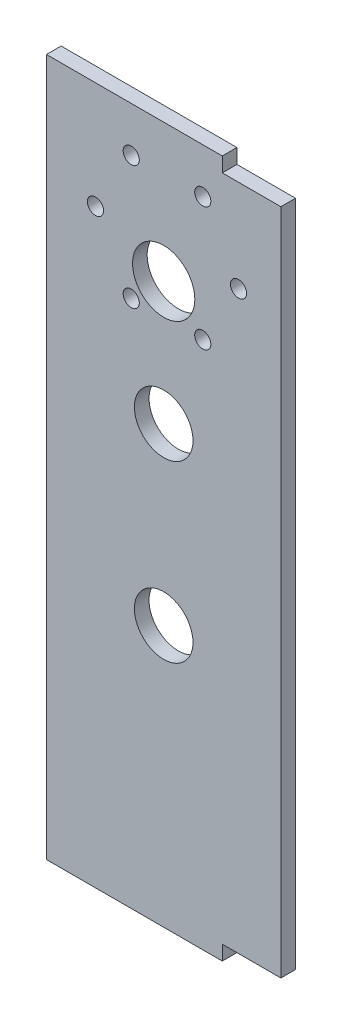
SolidWorks part; units mm, degrees
ref_plane "Спереди" through (0, 0, 0) normal (0, 0, 1) x (1, 0, 0)
ref_plane "Сверху" through (0, 0, 0) normal (0, 1, 0) x (1, 0, 0)
ref_plane "Справа" through (0, 0, 0) normal (1, 0, 0) x (0, 0, -1)
sketch "Эскиз1" plane through (0, 0, 0) normal (0, 0, 1) x (1, 0, 0)
  line L0 (6.35, 75.565) -> (6.35, 151.13) construction
  line L1 (19.05, 151.13) -> (-19.05, 151.13)
  line L13 (19.05, 0) -> (-19.05, 0)
  line L15 (-19.05, 0) -> (-19.05, 151.13)
  line L16 (19.05, 0) -> (19.05, 3.175)
  line L17 (19.05, 3.175) -> (31.75, 3.175)
  line L18 (31.75, 3.175) -> (31.75, 147.955)
  line L19 (31.75, 147.955) -> (19.05, 147.955)
  line L20 (19.05, 147.955) -> (19.05, 151.13)
  line L21 (-19.05, 75.565) -> (31.75, 75.565) construction
  line L22 (6.35, 75.565) -> (6.35, 107.9679) construction
  line L23 (22.5681, 127.955) -> (14.8181, 141.3784) construction
  line L24 (14.8181, 141.3784) -> (-0.6819, 141.3784) construction
  line L25 (-0.6819, 141.3784) -> (-8.4319, 127.955) construction
  line L26 (-8.4319, 127.955) -> (-0.6819, 114.5316) construction
  line L27 (-0.6819, 114.5316) -> (14.8181, 114.5316) construction
  line L28 (14.8181, 114.5316) -> (22.5681, 127.955) construction
  circle A0 centre (6.35, 56.6308) radius 18.9342 construction
  circle A8 centre (6.35, 94.4992) radius 18.9342 construction
  circle A9 centre (6.35, 121.2433) radius 6.75
  circle A10 centre (7.0681, 127.955) radius 13.4234 construction
  circle A12 centre (22.5681, 127.955) radius 1.75
  circle A13 centre (14.8181, 114.5316) radius 1.75
  circle A14 centre (-0.6819, 114.5316) radius 1.75
  circle A15 centre (-8.4319, 127.955) radius 1.75
  circle A16 centre (-0.6819, 141.3784) radius 1.75
  circle A17 centre (14.8181, 141.3784) radius 1.75
  circle A19 centre (7.0681, 127.955) radius 20 construction
  circle A20 centre (6.35, 121.2433) radius 7.81 construction
  circle A21 centre (6.35, 94.4992) radius 6.35
  circle A22 centre (6.35, 56.6308) radius 6.35
  point P22 (31.75, 75.565)
  point P23 (-19.05, 75.565)
  point P31 (0, 0)
  point P39 (7.0681, 114.5316)
  dimension "D6" = 13.5
  dimension "D8" = 40
  dimension "D9" = 32.4029
  dimension "D5" = 3.5
  dimension "D10" = 15.62
  dimension "D11" = 12.7
  dimension "D12" = 12.7
  dimension "D1" = 38.1
  dimension "D2" = 50.8
  dimension "D3" = 15.5
  dimension "D4" = 144.78
  dimension "D7" = 151.13
extrude "Бобышка-Вытянуть1" add sketch "Эскиз1" along normal blind 3.175
